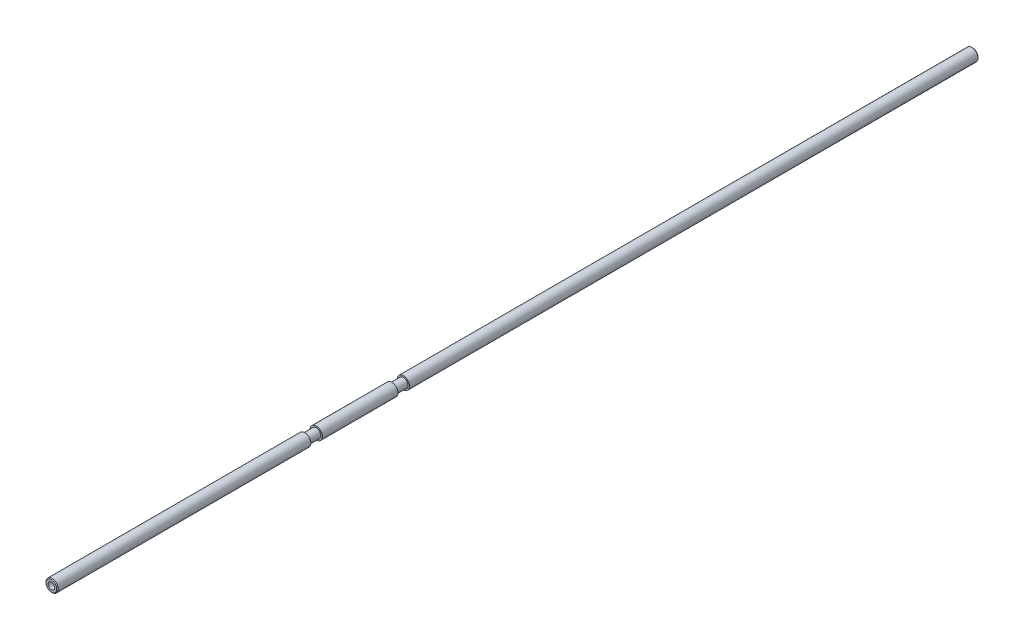
SolidWorks part; units mm, degrees
ref_plane "Front Plane" through (0, 0, 0) normal (0, 0, 1) x (1, 0, 0)
ref_plane "Top Plane" through (0, 0, 0) normal (0, 1, 0) x (1, 0, 0)
ref_plane "Right Plane" through (0, 0, 0) normal (1, 0, 0) x (0, 0, -1)
sketch "Sketch1" plane through (0, 0, 0) normal (0, 0, 1) x (1, 0, 0)
  circle A0 centre (45, 0) radius 8
  dimension "D1" = 16
  dimension "D2" = 45
extrude "Boss-Extrude1" add sketch "Sketch1" along normal blind 1200 from offset 10
chamfer "Chamfer1" distance 1 angle 45 2 edges at (53, 0, 1210) (53, 0, 10)
sketch "Sketch2" plane through (0, 0, 1210) normal (0, 0, 1) x (1, 0, 0)
  circle A0 centre (45, 0) radius 4.25
  dimension "D1" = 8.5
extrude "Cut-Extrude1" cut sketch "Sketch2" against normal blind 50
sketch "Sketch3" plane through (0, 0, 10) normal (0, 0, -1) x (-1, 0, 0)
  circle A0 centre (-45, 0) radius 4.25
  dimension "D1" = 8.5
extrude "Cut-Extrude2" cut sketch "Sketch3" against normal blind 50
sketch "Sketch4" plane through (0, 0, 10) normal (0, 0, -1) x (-1, 0, 0)
  circle A0 centre (-45, 0) radius 8 construction
  circle A1 centre (-45, 0) radius 8
  circle A2 centre (-45, 0) radius 6
  dimension "D1" = 12
sketch "Sketch5" plane through (0, 0, 1210) normal (0, 0, 1) x (1, 0, 0)
  circle A0 centre (45, 0) radius 6
  circle A1 centre (45, 0) radius 8 construction
  circle A2 centre (45, 0) radius 8
  dimension "D1" = 12
extrude "Cut-Extrude4" cut sketch "Sketch5" against normal blind 15 from offset 443.5 offset against normal yes
extrude "Cut-Extrude5" cut sketch "Sketch5<2>" against normal blind 15 from offset 330 offset against normal yes
sketch "Sketch5<2>" plane through (0, 0, 1210) normal (0, 0, 1) x (1, 0, 0) same geometry as "Sketch5"
